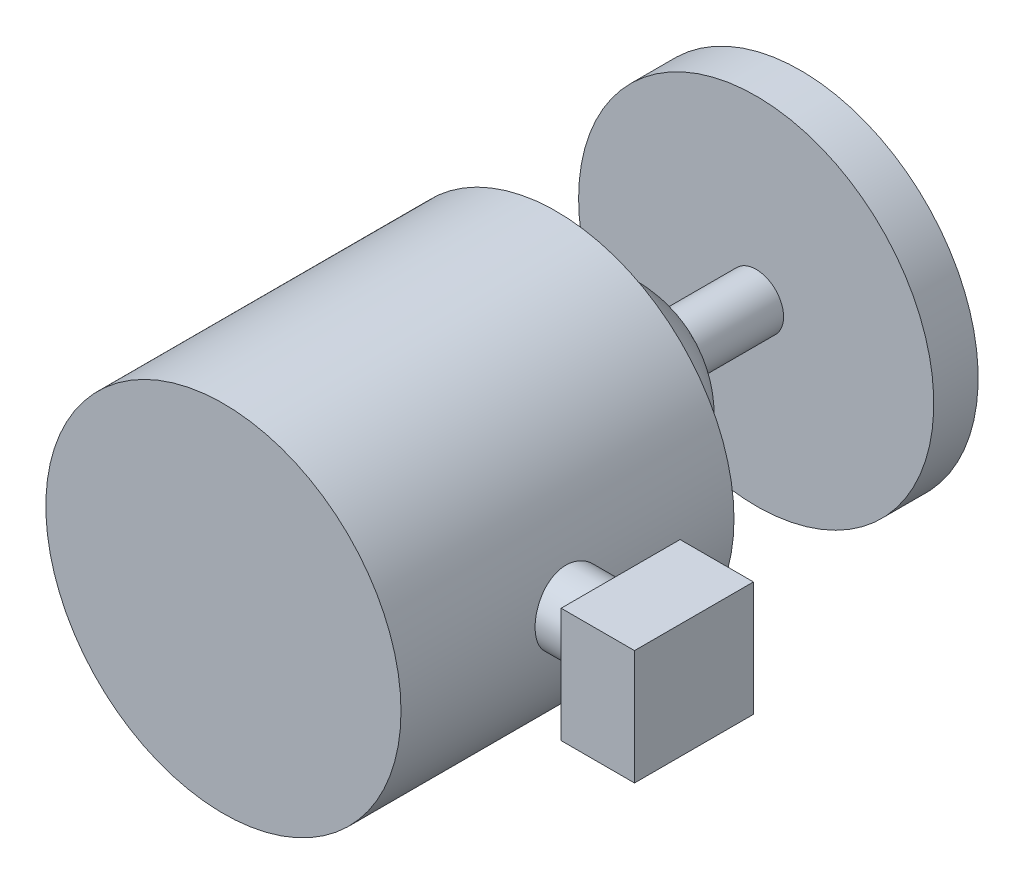
SolidWorks part; units mm, degrees
ref_plane "Front Plane" through (0, 0, 0) normal (0, 0, 1) x (1, 0, 0)
ref_plane "Top Plane" through (0, 0, 0) normal (0, 1, 0) x (1, 0, 0)
ref_plane "Right Plane" through (0, 0, 0) normal (1, 0, 0) x (0, 0, -1)
sketch "Sketch1" plane through (0, 0, 0) normal (0, 0, 1) x (1, 0, 0)
  circle A0 centre (0, 0) radius 16
extrude "Boss-Extrude1" add sketch "Sketch1" along normal blind 30
sketch "Sketch2" plane through (0, 0, 0) normal (1, 0, 0) x (0, 0, -1)
  circle A0 centre (-14.7381, 0.3869) radius 3.175
extrude "Boss-Extrude2" add sketch "Sketch2" along normal blind 20.582
sketch "Sketch3" plane through (20.582, 0, 0) normal (1, 0, 0) x (0, 0, -1)
  line L1 (-20.1554, -4.9321) -> (-9.4407, -4.9321)
  line L2 (-20.1554, -4.9321) -> (-20.1554, 5.3998)
  line L3 (-20.1554, 5.3998) -> (-9.4407, 5.3998)
  line L4 (-9.4407, -4.9321) -> (-9.4407, 5.3998)
  line L5 (-20.1554, -4.9321) -> (-9.4407, 5.3998) construction
  line L6 (-20.1554, 5.3998) -> (-9.4407, -4.9321) construction
  point P0 (-14.798, 0.2339)
extrude "Boss-Extrude3" add sketch "Sketch3" along normal blind 6.612
sketch "Sketch4" plane through (0, 0, 0) normal (0, 0, -1) x (-1, 0, 0)
  line L0 (-15.8495, -0.1631) -> (16, 0)
  circle A0 centre (0, 0) radius 10
  circle A1 centre (0, 0) radius 16 construction
revolve "Revolve1" add sketch "Sketch4" angle 360 about L0 region at (0.0215, 4.1998, 0)
sketch "Sketch5" plane through (0, 0, 0) normal (0, 0, -1) x (-1, 0, 0)
  circle A0 centre (0, 0) radius 2.4696
extrude "Boss-Extrude4" add sketch "Sketch5" along normal blind 28
sketch "Sketch6" plane through (0, 0, -28) normal (0, 0, -1) x (-1, 0, 0)
  circle A0 centre (0, 0) radius 16
extrude "Boss-Extrude5" add sketch "Sketch6" against normal blind 10
extrude "Cut-Extrude-Thin1" cut sketch "Sketch6<2>" against normal blind 6 thin thin type one direction reverse wall 13.5
sketch "Sketch6<2>" plane through (0, 0, -28) normal (0, 0, -1) x (-1, 0, 0) same geometry as "Sketch6"
